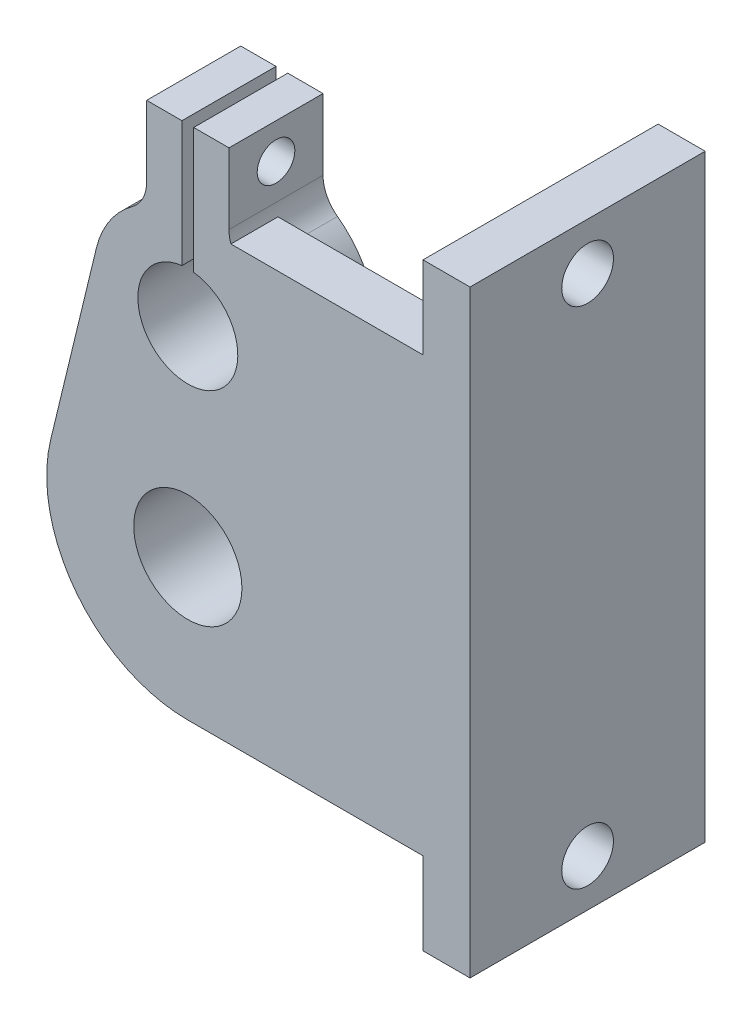
SolidWorks part; units mm, degrees
note: The reader was unsure of these and kept them because the rebuilt part matched: shared geometry of "草图1<4>", "草图1<5>", "草图4<3>".
ref_plane "前视基准面" through (0, 0, 0) normal (0, 0, 1) x (1, 0, 0)
ref_plane "上视基准面" through (0, 0, 0) normal (0, 1, 0) x (1, 0, 0)
ref_plane "右视基准面" through (0, 0, 0) normal (1, 0, 0) x (0, 0, -1)
sketch "草图1" plane through (0, 0, 0) normal (0, 0, 1) x (1, 0, 0)
  line L0 (-1000, 0) -> (49000, 0) construction
  line L1 (-999.6726, 42) -> (49000.3274, 42) construction
  line L2 (0, -1000) -> (0, 49000) construction
  line L3 (48, -1000) -> (48, 49000) construction
  line L4 (16.2246, 39.8824) -> (12.3369, 23.8235)
  line L5 (31.7754, 39.8824) -> (35.6631, 23.8235)
  line L6 (0, 52.8937) -> (0, 2)
  line L7 (0, 2) -> (4, 2)
  line L8 (4, 2) -> (4, 9)
  line L9 (4, 9) -> (44, 9)
  line L10 (0, 52.8937) -> (4, 52.8937)
  line L11 (4, 45.8937) -> (22.7005, 45.8937)
  line L12 (4, 45.8937) -> (4, 52.8937)
  line L13 (24, -979.5827) -> (24, 49020.4173) construction
  line L14 (20.5, 52.8937) -> (20.5, 46.8741)
  line L15 (20.5, 52.8937) -> (23.5, 52.8937)
  line L16 (23.5, 52.8937) -> (23.5, 42.2205)
  line L17 (24.5, 52.8937) -> (24.5, 42.2205)
  line L18 (27.5, 52.8937) -> (24.5, 52.8937)
  line L19 (27.5, 52.8937) -> (27.5, 46.8741)
  line L20 (48, 2) -> (44, 2)
  line L21 (44, 45.8937) -> (25.2995, 45.8937)
  line L22 (44, 45.8937) -> (44, 52.8937)
  line L23 (48, 52.8937) -> (48, 2)
  line L24 (48, 52.8937) -> (44, 52.8937)
  line L25 (44, 2) -> (44, 9)
  line L26 (4, 45.8937) -> (4, 9)
  line L27 (44, 45.8937) -> (44, 9)
  circle A0 centre (24, 21) radius 11.5 construction
  circle A1 centre (24, 38) radius 4 construction
  circle A2 centre (24, 21) radius 4.6
  arc A3 (23.5, 42.2205) -> (24.5, 42.2205) centre (24, 38) ccw
  arc A4 (31.7754, 39.8824) -> (28.7273, 44.4539) centre (24, 38) ccw
  arc A5 (12.3369, 23.8235) -> (35.6631, 23.8235) centre (24, 21) ccw
  arc A6 (19.2727, 44.4539) -> (16.2246, 39.8824) centre (24, 38) ccw
  arc A7 (20.5, 46.8741) -> (19.2727, 44.4539) centre (17.5, 46.8741) cw
  arc A8 (27.5, 46.8741) -> (28.7273, 44.4539) centre (30.5, 46.8741) ccw
  point P39 (24, 9)
  point P45 (20.5, 45.1937)
  point P48 (27.5, 45.1937)
  dimension "D3" = 8.5
  dimension "D4" = 9.2
  dimension "D5" = 8
  dimension "D6" = 24
  dimension "D13" = 3
  dimension "D1" = 48
  dimension "D2" = 42
  dimension "D7" = 4
  dimension "D8" = 3
  dimension "D9" = 0.5
  dimension "D10" = 7.7
  dimension "D11" = 7
  dimension "D12" = 7
extrude "凸台-拉伸1" add sketch "草图1" along normal blind 4 contours L14 A6 L4 A5 L5 A4 L19 L18 L17 A3 L16 L15 A2 | A5 L9 L27 L21 A4 L5 | L22 L27 L25 L20 L23 L24
extrude "凸台-拉伸2" add sketch "草图1<4>" against normal blind 4 contours L22 L27 L25 L20 L23 L24 | A8 L19 L18 L17 A3 L16 L15 L14 A7 A6 L4 A5 L5 A4 A2
sketch "草图1<4>" plane through (0, 0, 0) normal (0, 0, 1) x (1, 0, 0) same geometry as "草图1"
extrude "凸台-拉伸3" add sketch "草图1<5>" against normal blind 12 from surface at -4 contours L22 L27 L25 L20 L23 L24 starting at face at (46, 27.4469, -4)
sketch "草图1<5>" plane through (0, 0, 0) normal (0, 0, 1) x (1, 0, 0) same geometry as "草图1"
sketch "草图4" plane through (44, 0, 0) normal (1, 0, 0) x (0, 0, -1)
  line L0 (16, 2) -> (16, 52.8937) construction
  line L1 (-4, 39.8824) -> (-4, 23.8235) construction
  line L3 (16, 27.4469) -> (-4, 27.4469) construction
  line L6 (-4, 2) -> (16, 2) construction
  circle A0 centre (0, 49.8937) radius 1.6
  circle A1 centre (6, 6) radius 2.2
  circle A2 centre (6, 48.8937) radius 2.2
  circle A3 centre (6, 6) radius 4 construction
  circle A4 centre (6, 48.8937) radius 4 construction
  circle A5 centre (6, 6) radius 1.5 construction
  circle A6 centre (6, 48.8937) radius 1.5 construction
  dimension "D1" = 3.2
  dimension "D4" = 4.4
  dimension "D6" = 8
  dimension "D5" = 3
  dimension "D2" = 3
  dimension "D3" = 6
extrude "切除-拉伸2" cut sketch "草图4" along normal through all contours A1 | A2
extrude "切除-拉伸3" cut sketch "草图4<3>" against normal through all contours A0
sketch "草图4<3>" plane through (44, 0, 0) normal (1, 0, 0) x (0, 0, -1) same geometry as "草图4"
ref_plane "基准面1" through (0, 19, 0) normal (0, -1, 0) x (-1, 0, 0)
ref_plane "基准面2" through (0, 35.8937, 0) normal (0, 1, 0) x (1, 0, 0)
sketch "草图6" plane through (0, 19, 0) normal (0, -1, 0) x (-1, 0, 0)
  line L0 (-4, 14) -> (-10, 0) construction
  line L2 (-24, -996) -> (-24, 49004) construction
  line L3 (-19.75, 4) -> (-28.25, 4) construction
  line L4 (-44, 14) -> (-38, 0)
  point P7 (-24, 4)
  dimension "D1" = 14
  dimension "D2" = 10
rib "筋6" sketch "草图6" sketch "草图6" thickness 5 extrusion direction parallel to sketch draft on no parameters "D1"=5
sketch "草图8" plane through (0, 35.8937, 0) normal (0, 1, 0) x (1, 0, 0)
  line L1 (44, 14) -> (38, 0) construction
  line L2 (44, 14) -> (38, 0)
rib "筋7" sketch "草图8" sketch "草图8" thickness 5 extrusion direction parallel to sketch draft on no parameters "D1"=5
